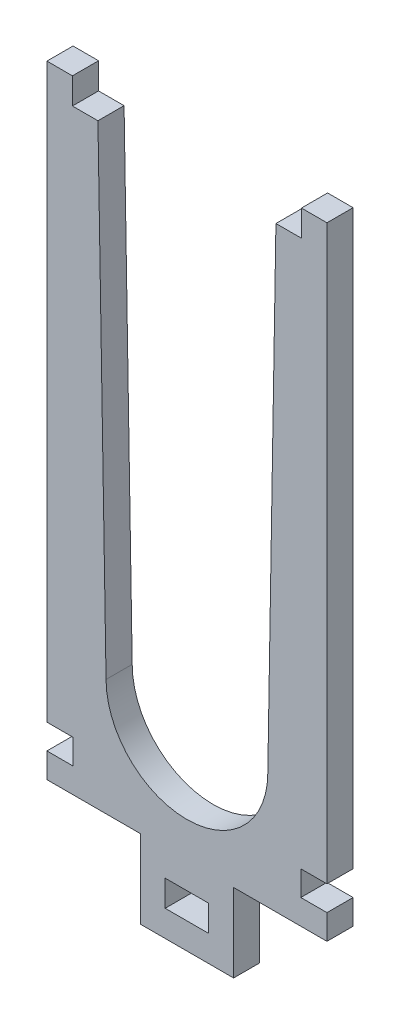
SolidWorks part; units mm, degrees
ref_plane "Front Plane" through (0, 0, 0) normal (0, 0, 1) x (1, 0, 0)
ref_plane "Top Plane" through (0, 0, 0) normal (0, 1, 0) x (1, 0, 0)
ref_plane "Right Plane" through (0, 0, 0) normal (1, 0, 0) x (0, 0, -1)
sketch "Sketch8" plane through (0, 0, 0) normal (0, 0, 1) x (1, 0, 0)
  line L1 (0, 0) -> (57.15, 0)
  line L2 (0, 0) -> (0, 127)
  line L3 (0, 127) -> (57.15, 127)
  line L4 (57.15, 0) -> (57.15, 127)
  dimension "D1" = 57.15
  dimension "D2" = 127
extrude "Boss-Extrude3" add sketch "Sketch8" along normal blind 5.334
sketch "Sketch9" plane through (0, 0, 5.334) normal (0, 0, 1) x (1, 0, 0)
  line L0 (0, 127) -> (10.414, 127)
  line L1 (57.15, 127) -> (0, 127) construction
  line L2 (28.575, 0) -> (28.575, 12.573) construction
  line L3 (57.15, 127) -> (46.736, 127)
  line L4 (57.15, 127) -> (46.736, 127)
  line L5 (0, 0) -> (57.15, 0) construction
  line L6 (28.575, 29.083) -> (28.575, 12.573) construction
  line L7 (10.414, 127) -> (12.0698, 29.083)
  line L8 (46.736, 127) -> (45.0802, 29.083)
  circle A0 centre (28.575, 29.083) radius 16.5052
  line M9 (57.15, 127) -> (0, 127)
  dimension "D1" = 10.414
  dimension "D2" = 10.414
  dimension "D3" = 12.573
  dimension "D4" = 16.51
extrude "Cut-Extrude4" cut sketch "Sketch9" against normal through all contours A0 L8 L7 M9 | A0 region at (28.575, 84.9853, 5.334) region at (28.575, 29.083, 5.334)
sketch "Sketch12" plane through (0, 0, 0) normal (0, -1, 0) x (-1, 0, 0)
  line L0 (0, -5.334) -> (-57.15, -5.334) construction
  line L1 (-57.15, 0) -> (-38.1, 0)
  line L2 (-57.15, 0) -> (-57.15, -5.334)
  line L3 (-57.15, -5.334) -> (-38.1, -5.334)
  line L4 (-38.1, 0) -> (-38.1, -5.334)
  line L5 (-38.1, -5.334) -> (-19.05, -5.334) construction
  line L6 (0, 0) -> (-19.05, 0)
  line L7 (0, 0) -> (0, -5.334)
  line L8 (0, -5.334) -> (-19.05, -5.334)
  line L9 (-19.05, 0) -> (-19.05, -5.334)
extrude "Cut-Extrude8" cut sketch "Sketch12" against normal blind 5.334
sketch "Sketch14" plane through (0, 127, 0) normal (0, 1, 0) x (1, 0, 0)
  line L1 (46.736, 0) -> (57.15, 0)
  line L2 (46.736, 0) -> (46.736, -5.334)
  line L3 (46.736, -5.334) -> (57.15, -5.334)
  line L4 (57.15, 0) -> (57.15, -5.334)
  line L5 (0, 0) -> (10.414, 0)
  line L6 (0, 0) -> (0, -5.334)
  line L7 (0, -5.334) -> (10.414, -5.334)
  line L8 (10.414, 0) -> (10.414, -5.334)
extrude "Boss-Extrude4" add sketch "Sketch14" along normal blind 5.334
sketch "Sketch15" plane through (0, 132.334, 0) normal (0, 1, 0) x (1, 0, 0)
  line L0 (0, -5.334) -> (10.414, -5.334) construction
  line L1 (10.414, 0) -> (5.207, 0)
  line L2 (10.414, 0) -> (10.414, -5.334)
  line L3 (10.414, -5.334) -> (5.207, -5.334)
  line L4 (5.207, 0) -> (5.207, -5.334)
  line L5 (5.207, 0) -> (0, 0) construction
  line L6 (46.736, -5.334) -> (57.15, -5.334) construction
  line L7 (46.736, 0) -> (51.943, 0)
  line L8 (46.736, 0) -> (46.736, -5.334)
  line L9 (46.736, -5.334) -> (51.943, -5.334)
  line L10 (51.943, 0) -> (51.943, -5.334)
  line L11 (51.943, 0) -> (57.15, 0) construction
extrude "Cut-Extrude9" cut sketch "Sketch15" against normal blind 5.334
sketch "Sketch22" plane through (0, 0, 0) normal (0, -1, 0) x (1, 0, 0)
  line L1 (38.1, 0) -> (19.05, 0)
  line L2 (38.1, 0) -> (38.1, 5.334)
  line L3 (38.1, 5.334) -> (19.05, 5.334)
  line L4 (19.05, 0) -> (19.05, 5.334)
extrude "Boss-Extrude5" add sketch "Sketch22" along normal blind 10.668
sketch "Sketch23" plane through (0, 0, 0) normal (0, 0, -1) x (-1, 0, 0)
  line L0 (-19.05, -10.668) -> (-38.1, -10.668) construction
  line L1 (-33.02, 0) -> (-24.13, 0)
  line L2 (-33.02, 0) -> (-33.02, -5.334)
  line L3 (-33.02, -5.334) -> (-24.13, -5.334)
  line L4 (-24.13, 0) -> (-24.13, -5.334)
  line L5 (-19.05, 5.334) -> (-19.05, -10.668) construction
  line L6 (-38.1, 5.334) -> (-38.1, -10.668) construction
  dimension "D1" = 5.334
  dimension "D2" = 5.334
  dimension "D3" = 5.08
  dimension "D4" = 8.89
  dimension "D5" = 5.08
extrude "Cut-Extrude15" cut sketch "Sketch23" against normal through all
sketch "Sketch24" plane through (0, 0, 0) normal (0, 0, -1) x (-1, 0, 0)
  line L0 (-57.15, 5.334) -> (0, 5.334) construction
  line L1 (-28.575, 5.334) -> (-28.575, 23.0561) construction
  line L2 (-57.15, 5.334) -> (-57.15, 132.334) construction
  line L3 (-57.15, 10.414) -> (-51.816, 10.414)
  line L4 (-57.15, 10.414) -> (-57.15, 15.494)
  line L5 (-57.15, 15.494) -> (-51.816, 15.494)
  line L6 (-51.816, 10.414) -> (-51.816, 15.494)
  line L7 (-5.334, 10.414) -> (-5.334, 15.494)
  line L8 (0, 15.494) -> (-5.334, 15.494)
  line L9 (0, 10.414) -> (0, 15.494)
  line L10 (0, 10.414) -> (-5.334, 10.414)
  dimension "D1" = 5.08
  dimension "D2" = 5.08
  dimension "D3" = 5.334
extrude "Cut-Extrude16" cut sketch "Sketch24" against normal through all
equation "\"Foamcore\"= .1875in"
equation "\"Mdf\"= .21in"
equation "\"Gmaterial\"= \"Mdf\""
equation "\"D1@Boss-Extrude3\"= \"Gmaterial\""
equation "\"D1@Cut-Extrude9\"=\"Gmaterial\""
equation "\"D1@Cut-Extrude8\"=\"Gmaterial\""
equation "\"D1@Boss-Extrude4\"= \"Gmaterial\""
equation "\"D2@Sketch9\"=0.41in"
equation "\"D1@Sketch9\"=0.41in"
equation "\"D2@Sketch8\"=5in"
equation "\"D3@Sketch9\"=0.495in"
